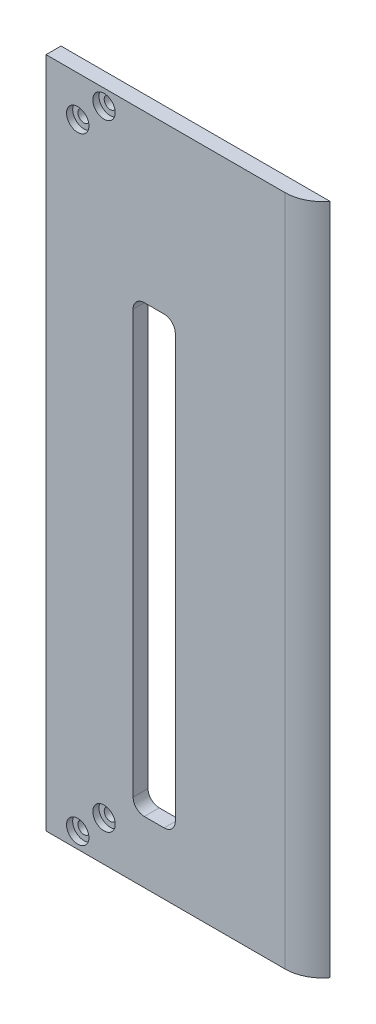
SolidWorks part; units mm, degrees
ref_plane "Alzado" through (0, 0, 0) normal (0, 0, 1) x (1, 0, 0)
ref_plane "Planta" through (0, 0, 0) normal (0, 1, 0) x (1, 0, 0)
ref_plane "Vista lateral" through (0, 0, 0) normal (1, 0, 0) x (0, 0, -1)
sketch "Croquis1" plane through (0, 0, 0) normal (0, 0, 1) x (1, 0, 0)
  line L0 (-10, 162.7734) -> (62, 162.7734) construction
  line L1 (-10, 72.7734) -> (62, 72.7734)
  line L2 (-10, 72.7734) -> (-10, 252.7734)
  line L3 (-10, 252.7734) -> (62, 252.7734)
  line L4 (62, 72.7734) -> (62, 252.7734)
  line L5 (-10, 72.7734) -> (62, 252.7734) construction
  line L6 (-10, 252.7734) -> (62, 72.7734) construction
  line L7 (-6, 72.7734) -> (10, 72.7734)
  line L8 (-6, 72.7734) -> (-6, 87.7734) construction
  line L9 (-6, 87.7734) -> (10, 87.7734) construction
  line L10 (10, 72.7734) -> (10, 87.7734) construction
  line L11 (-6, 72.7734) -> (10, 87.7734) construction
  line L12 (-6, 87.7734) -> (10, 72.7734) construction
  line L13 (-6, 252.7734) -> (-6, 237.7734) construction
  line L14 (-6, 237.7734) -> (10, 252.7734) construction
  line L15 (-6, 252.7734) -> (10, 237.7734) construction
  line L16 (10, 252.7734) -> (10, 237.7734) construction
  line L17 (-6, 237.7734) -> (10, 237.7734) construction
  line L18 (62, 72.7734) -> (62, 252.7734) construction
  line L19 (-6, 252.7734) -> (58, 252.7734) construction
  circle A12 centre (-1.52, 76.9734) radius 1.6
  circle A13 centre (5.52, 83.5734) radius 1.6
  circle A15 centre (-1.52, 241.9734) radius 1.6
  circle A16 centre (5.52, 248.5734) radius 1.6
  point P4 (26, 162.7734)
  point P11 (2, 80.2734)
  point P24 (2, 245.2734)
  dimension "D1" = 16
  dimension "D2" = 15
  dimension "D4" = 3.2
  dimension "D5" = 3.2
  dimension "D8" = 4.2
  dimension "D10" = 3.2
  dimension "D3" = 4
  dimension "D6" = 4.2
  dimension "D7" = 4.2
  dimension "D9" = 4.2
extrude "Saliente-Extruir1" add sketch "Croquis1" along normal blind 4 contours A13 | L1 L4 L3 L2 | A12 region at (26.0597, 162.7734, 0)
sketch "Croquis2" plane through (0, 0, 4) normal (0, 0, 1) x (1, 0, 0)
  line L0 (-10, 72.7734) -> (62, 72.7734) construction
  line L1 (-6, 72.7734) -> (10, 72.7734) construction
  line L2 (-6, 72.7734) -> (-6, 87.7734) construction
  line L3 (-6, 87.7734) -> (10, 87.7734) construction
  line L4 (10, 72.7734) -> (10, 87.7734) construction
  line L5 (-6, 72.7734) -> (10, 87.7734) construction
  line L6 (-6, 87.7734) -> (10, 72.7734) construction
  line L7 (-10, 72.7734) -> (-10, 252.7734) construction
  line L8 (-10, 162.7734) -> (62, 162.7734) construction
  line L9 (62, 72.7734) -> (62, 252.7734) construction
  line L10 (-6, 237.7734) -> (10, 252.7734) construction
  line L11 (-6, 252.7734) -> (10, 237.7734) construction
  line L12 (10, 252.7734) -> (10, 237.7734) construction
  line L13 (-6, 237.7734) -> (10, 237.7734) construction
  line L14 (-6, 252.7734) -> (-6, 237.7734) construction
  line L15 (-6, 252.7734) -> (10, 252.7734) construction
  circle A8 centre (-1.52, 76.9734) radius 3
  circle A9 centre (5.52, 83.5734) radius 3
  circle A12 centre (-1.52, 241.9734) radius 3
  circle A13 centre (5.52, 248.5734) radius 3
  point P16 (2, 80.2734)
  point P26 (2, 245.2734)
  dimension "D4" = 6
  dimension "D7" = 4.2
  dimension "D9" = 6
  dimension "D1" = 15
  dimension "D2" = 16
  dimension "D3" = 4
  dimension "D5" = 4.2
  dimension "D6" = 4.2
  dimension "D8" = 4.2
extrude "Cortar-Extruir1" cut sketch "Croquis2" against normal blind 1.65
sketch "Croquis3" plane through (0, 0, 0) normal (0, 0, -1) x (-1, 0, 0)
  line L0 (6, 162.7734) -> (-62, 162.7734) construction
  line L2 (-62, 72.7734) -> (-62, 252.7734) construction
  line L3 (10, 72.7734) -> (10, 252.7734) construction
  line L4 (6, 200.2734) -> (-62, 200.2734) construction
  line L10 (6, 120.2734) -> (1, 120.2734)
  line L11 (6, 120.2734) -> (6, 130.2734)
  line L12 (6, 130.2734) -> (1, 130.2734)
  line L13 (6, 125.2734) -> (-62, 125.2734) construction
  line L18 (1, 120.2734) -> (1, 130.2734)
  line L19 (6, 195.2734) -> (1, 195.2734)
  line L20 (6, 195.2734) -> (6, 205.2734)
  line L21 (6, 205.2734) -> (1, 205.2734)
  line L22 (1, 195.2734) -> (1, 205.2734)
  dimension "D1" = 37.5
  dimension "D2" = 5
  dimension "D3" = 10
  dimension "D4" = 10
  dimension "D5" = 4
  dimension "D6" = 5
extrude "Saliente-Extruir2" add sketch "Croquis3" along normal blind 10
sketch "Croquis4" plane through (-6, 0, 0) normal (-1, 0, 0) x (0, 0, 1)
  line L1 (0, 195.2734) -> (-10, 195.2734)
  line L2 (0, 195.2734) -> (0, 205.2734)
  line L3 (0, 205.2734) -> (-10, 205.2734)
  line L4 (-10, 195.2734) -> (-10, 205.2734)
  line L5 (0, 195.2734) -> (-10, 205.2734) construction
  line L6 (0, 205.2734) -> (-10, 195.2734) construction
  line L7 (0, 120.2734) -> (-10, 120.2734)
  line L8 (0, 120.2734) -> (0, 130.2734)
  line L9 (0, 130.2734) -> (-10, 130.2734)
  line L10 (-10, 120.2734) -> (-10, 130.2734)
  line L11 (0, 120.2734) -> (-10, 130.2734) construction
  line L12 (0, 130.2734) -> (-10, 120.2734) construction
  line L13 (-3.4123, 122.5234) -> (-1.8246, 125.2734)
  line L14 (-1.8246, 125.2734) -> (-3.4123, 128.0234)
  line L15 (-3.4123, 128.0234) -> (-6.5877, 128.0234)
  line L16 (-6.5877, 128.0234) -> (-8.1754, 125.2734)
  line L17 (-8.1754, 125.2734) -> (-6.5877, 122.5234)
  line L18 (-6.5877, 122.5234) -> (-3.4123, 122.5234)
  line L19 (-3.4123, 197.5234) -> (-1.8246, 200.2734)
  line L20 (-1.8246, 200.2734) -> (-3.4123, 203.0234)
  line L21 (-3.4123, 203.0234) -> (-6.5877, 203.0234)
  line L22 (-6.5877, 203.0234) -> (-8.1754, 200.2734)
  line L23 (-8.1754, 200.2734) -> (-6.5877, 197.5234)
  line L24 (-6.5877, 197.5234) -> (-3.4123, 197.5234)
  circle A0 centre (-5, 200.2734) radius 1.5
  circle A1 centre (-5, 125.2734) radius 1.5
  circle A2 centre (-5, 125.2734) radius 2.75 construction
  circle A3 centre (-5, 200.2734) radius 2.75 construction
  point P4 (-5, 200.2734)
  point P13 (-5, 125.2734)
  dimension "D1" = 5.5
  dimension "D2" = 3
  dimension "D4" = 3
  dimension "D3" = 5.5
  dimension "D5" = 10
  dimension "D6" = 10
extrude "Cortar-Extruir2" cut sketch "Croquis4" against normal up to next contours A1 | A0 region at (-6, 200.2734, -5) region at (-6, 125.2734, -5)
extrude "Cortar-Extruir3" cut sketch "Croquis4<3>" against normal blind 1.65 contours L23 L24 L19 L20 L21 L22 A0 | L17 L18 L13 L14 L15 L16 A1 region at (-6, 122.6074, -5) region at (-6, 197.6074, -5)
sketch "Croquis4<3>" plane through (-6, 0, 0) normal (-1, 0, 0) x (0, 0, 1) same geometry as "Croquis4"
fillet "Redondeo2" radius 10 1 edges at (62, 162.7734, 4)
sketch "Croquis5" plane through (0, 0, 0) normal (0, 0, -1) x (-1, 0, 0)
  line L0 (-21.4, 186.4179) -> (-21.4, 188.4134) construction
  line L10 (-21.4, 188.7334) -> (-21.4, 190.7289) construction
  line L11 (-21.2596, 191.0555) -> (-20.5798, 191.7) construction
  line L12 (-20.2702, 191.8234) -> (-18.95, 191.8234) construction
  line L13 (-18.5, 191.3734) -> (-18.5, 185.7734) construction
  line L14 (-18.95, 185.3234) -> (-20.2702, 185.3234) construction
  line L15 (-20.5798, 185.4468) -> (-21.2596, 186.0913) construction
  line L16 (-21.4, 199.8179) -> (-21.4, 201.8134) construction
  line L26 (-21.4, 202.1334) -> (-21.4, 204.1289) construction
  line L27 (-21.2596, 204.4555) -> (-20.5798, 205.1) construction
  line L28 (-20.2702, 205.2234) -> (-18.95, 205.2234) construction
  line L29 (-18.5, 204.7734) -> (-18.5, 199.1734) construction
  line L30 (-18.95, 198.7234) -> (-20.2702, 198.7234) construction
  line L31 (-20.5798, 198.8468) -> (-21.2596, 199.4913) construction
  line L32 (-19.54, 169.5034) -> (-20.1, 169.5034) construction
  line L33 (-21.4, 170.8034) -> (-21.4, 177.1434) construction
  line L34 (-20.1, 178.4434) -> (-19.54, 178.4434) construction
  line L35 (-18.24, 177.1434) -> (-18.24, 170.8034) construction
  line L36 (-21.4, 186.4179) -> (-21.4, 188.4134) construction
  line L46 (-21.4, 188.4134) -> (-21.4, 190.7289) construction
  line L47 (-21.2596, 191.0555) -> (-20.5798, 191.7) construction
  line L48 (-20.2702, 191.8234) -> (-18.95, 191.8234) construction
  line L49 (-18.5, 191.3734) -> (-18.5, 185.7734) construction
  line L50 (-18.95, 185.3234) -> (-20.2702, 185.3234) construction
  line L51 (-20.5798, 185.4468) -> (-21.2596, 186.0913) construction
  line L52 (-21.4, 199.8179) -> (-21.4, 201.8134) construction
  line L62 (-21.4, 201.8134) -> (-21.4, 204.1289) construction
  line L63 (-21.2596, 204.4555) -> (-20.5798, 205.1) construction
  line L64 (-20.2702, 205.2234) -> (-18.95, 205.2234) construction
  line L65 (-18.5, 204.7734) -> (-18.5, 199.1734) construction
  line L66 (-18.95, 198.7234) -> (-20.2702, 198.7234) construction
  line L67 (-20.5798, 198.8468) -> (-21.2596, 199.4913) construction
  line L68 (-19.54, 169.5034) -> (-20.1, 169.5034) construction
  line L69 (-21.4, 170.8034) -> (-21.4, 177.1434) construction
  line L70 (-20.1, 178.4434) -> (-19.54, 178.4434) construction
  line L71 (-18.24, 177.1434) -> (-18.24, 170.8034) construction
  line L72 (-18.04, 177.1434) -> (-18.04, 170.8034)
  line L73 (-19.54, 169.3034) -> (-20.1, 169.3034)
  line L74 (-21.6, 170.8034) -> (-21.6, 177.1434)
  line L75 (-20.1, 178.6434) -> (-19.54, 178.6434)
  line L76 (-18.3, 191.3734) -> (-18.3, 185.7734)
  line L77 (-18.95, 185.1234) -> (-20.2702, 185.1234)
  line L78 (-20.7174, 185.3017) -> (-21.3972, 185.9462)
  line L79 (-21.6, 186.4179) -> (-21.6, 188.4134)
  line L80 (-21.6, 188.4134) -> (-21.6, 190.7289)
  line L81 (-21.3972, 191.2006) -> (-20.7174, 191.8451)
  line L82 (-20.2702, 192.0234) -> (-18.95, 192.0234)
  line L83 (-18.95, 198.5234) -> (-20.2702, 198.5234)
  line L84 (-20.7174, 198.7017) -> (-21.3972, 199.3462)
  line L85 (-21.6, 199.8179) -> (-21.6, 201.8134)
  line L86 (-21.6, 201.8134) -> (-21.6, 204.1289)
  line L87 (-21.3972, 204.6006) -> (-20.7174, 205.2451)
  line L88 (-20.2702, 205.4234) -> (-18.95, 205.4234)
  line L89 (-18.3, 204.7734) -> (-18.3, 199.1734)
  arc A6 (-21.2596, 191.0555) -> (-21.4, 190.7289) centre (-20.95, 190.7289) ccw construction
  arc A7 (-20.2702, 191.8234) -> (-20.5798, 191.7) centre (-20.2702, 191.3734) ccw construction
  arc A8 (-18.5, 191.3734) -> (-18.95, 191.8234) centre (-18.95, 191.3734) ccw construction
  arc A9 (-18.95, 185.3234) -> (-18.5, 185.7734) centre (-18.95, 185.7734) ccw construction
  arc A10 (-20.5798, 185.4468) -> (-20.2702, 185.3234) centre (-20.2702, 185.7734) ccw construction
  arc A11 (-21.4, 186.4179) -> (-21.2596, 186.0913) centre (-20.95, 186.4179) ccw construction
  arc A18 (-21.2596, 204.4555) -> (-21.4, 204.1289) centre (-20.95, 204.1289) ccw construction
  arc A19 (-20.2702, 205.2234) -> (-20.5798, 205.1) centre (-20.2702, 204.7734) ccw construction
  arc A20 (-18.5, 204.7734) -> (-18.95, 205.2234) centre (-18.95, 204.7734) ccw construction
  arc A21 (-18.95, 198.7234) -> (-18.5, 199.1734) centre (-18.95, 199.1734) ccw construction
  arc A22 (-20.5798, 198.8468) -> (-20.2702, 198.7234) centre (-20.2702, 199.1734) ccw construction
  arc A23 (-21.4, 199.8179) -> (-21.2596, 199.4913) centre (-20.95, 199.8179) ccw construction
  arc A24 (-21.4, 170.8034) -> (-20.1, 169.5034) centre (-20.1, 170.8034) ccw construction
  arc A25 (-20.1, 178.4434) -> (-21.4, 177.1434) centre (-20.1, 177.1434) ccw construction
  arc A26 (-18.24, 177.1434) -> (-19.54, 178.4434) centre (-19.54, 177.1434) ccw construction
  arc A27 (-19.54, 169.5034) -> (-18.24, 170.8034) centre (-19.54, 170.8034) ccw construction
  arc A34 (-21.2596, 191.0555) -> (-21.4, 190.7289) centre (-20.95, 190.7289) ccw construction
  arc A35 (-20.2702, 191.8234) -> (-20.5798, 191.7) centre (-20.2702, 191.3734) ccw construction
  arc A36 (-18.5, 191.3734) -> (-18.95, 191.8234) centre (-18.95, 191.3734) ccw construction
  arc A37 (-18.95, 185.3234) -> (-18.5, 185.7734) centre (-18.95, 185.7734) ccw construction
  arc A38 (-20.5798, 185.4468) -> (-20.2702, 185.3234) centre (-20.2702, 185.7734) ccw construction
  arc A39 (-21.4, 186.4179) -> (-21.2596, 186.0913) centre (-20.95, 186.4179) ccw construction
  arc A46 (-21.2596, 204.4555) -> (-21.4, 204.1289) centre (-20.95, 204.1289) ccw construction
  arc A47 (-20.2702, 205.2234) -> (-20.5798, 205.1) centre (-20.2702, 204.7734) ccw construction
  arc A48 (-18.5, 204.7734) -> (-18.95, 205.2234) centre (-18.95, 204.7734) ccw construction
  arc A49 (-18.95, 198.7234) -> (-18.5, 199.1734) centre (-18.95, 199.1734) ccw construction
  arc A50 (-20.5798, 198.8468) -> (-20.2702, 198.7234) centre (-20.2702, 199.1734) ccw construction
  arc A51 (-21.4, 199.8179) -> (-21.2596, 199.4913) centre (-20.95, 199.8179) ccw
  arc A52 (-21.4, 170.8034) -> (-20.1, 169.5034) centre (-20.1, 170.8034) ccw construction
  arc A53 (-20.1, 178.4434) -> (-21.4, 177.1434) centre (-20.1, 177.1434) ccw construction
  arc A54 (-18.24, 177.1434) -> (-19.54, 178.4434) centre (-19.54, 177.1434) ccw construction
  arc A55 (-19.54, 169.5034) -> (-18.24, 170.8034) centre (-19.54, 170.8034) ccw construction
  arc A56 (-19.54, 169.3034) -> (-18.04, 170.8034) centre (-19.54, 170.8034) ccw
  arc A57 (-21.6, 170.8034) -> (-20.1, 169.3034) centre (-20.1, 170.8034) ccw
  arc A58 (-20.1, 178.6434) -> (-21.6, 177.1434) centre (-20.1, 177.1434) ccw
  arc A59 (-18.04, 177.1434) -> (-19.54, 178.6434) centre (-19.54, 177.1434) ccw
  arc A60 (-18.95, 185.1234) -> (-18.3, 185.7734) centre (-18.95, 185.7734) ccw
  arc A61 (-20.7174, 185.3017) -> (-20.2702, 185.1234) centre (-20.2702, 185.7734) ccw
  arc A62 (-21.6, 186.4179) -> (-21.3972, 185.9462) centre (-20.95, 186.4179) ccw
  arc A63 (-21.3972, 191.2006) -> (-21.6, 190.7289) centre (-20.95, 190.7289) ccw
  arc A64 (-20.2702, 192.0234) -> (-20.7174, 191.8451) centre (-20.2702, 191.3734) ccw
  arc A65 (-18.3, 191.3734) -> (-18.95, 192.0234) centre (-18.95, 191.3734) ccw
  arc A66 (-20.7174, 198.7017) -> (-20.2702, 198.5234) centre (-20.2702, 199.1734) ccw
  arc A67 (-21.6, 199.8179) -> (-21.3972, 199.3462) centre (-20.95, 199.8179) ccw
  arc A68 (-21.3972, 204.6006) -> (-21.6, 204.1289) centre (-20.95, 204.1289) ccw
  arc A69 (-20.2702, 205.4234) -> (-20.7174, 205.2451) centre (-20.2702, 204.7734) ccw
  arc A70 (-18.3, 204.7734) -> (-18.95, 205.4234) centre (-18.95, 204.7734) ccw
  arc A71 (-18.95, 198.5234) -> (-18.3, 199.1734) centre (-18.95, 199.1734) ccw
  dimension "D1" = 0.2
extrude "Cortar-Extruir4" cut sketch "Croquis5" against normal up to next contours L72 A59 L75 A58 L74 A57 L73 A56 | L76 A65 L82 A64 L81 A63 L80 L79 A62 L78 A61 L77 A60 | L83 A71 L89 A70 L88 A69 L87 A68 L86 L85 A67 L84 A66 region at (19.82, 173.9734, 0) region at (19.8953, 188.5734, 0) region at (19.8953, 201.9734, 0)
sketch "Croquis6" plane through (0, 0, 4) normal (0, 0, 1) x (1, 0, 0)
  line L0 (20.2702, 205.4234) -> (18.95, 205.4234) construction
  line L1 (13.3, 89.3034) -> (24.6, 89.3034)
  line L2 (13.3, 89.3034) -> (13.3, 208.4234)
  line L3 (13.3, 208.4234) -> (24.6, 208.4234)
  line L4 (24.6, 89.3034) -> (24.6, 208.4234)
  line L5 (13.3, 89.3034) -> (24.6, 208.4234) construction
  line L6 (13.3, 208.4234) -> (24.6, 89.3034) construction
  line L7 (21.6, 186.4179) -> (21.6, 190.7289) construction
  line L8 (18.3, 191.3734) -> (18.3, 185.7734) construction
  line L9 (19.54, 169.3034) -> (20.1, 169.3034) construction
  point P4 (18.95, 148.8634)
  point P7 (19.6101, 205.4234)
  dimension "D1" = 3
  dimension "D2" = 3
  dimension "D3" = 5
  dimension "D4" = 80
extrude "Cortar-Extruir5" cut sketch "Croquis6" against normal up to surface (4 mm away) up to face at (20.1943, 188.5734, 0)
fillet "Redondeo3" radius 3 4 edges at (24.6, 89.3034, 2) (24.6, 208.4234, 2) (13.3, 208.4234, 2) (13.3, 89.3034, 2)
